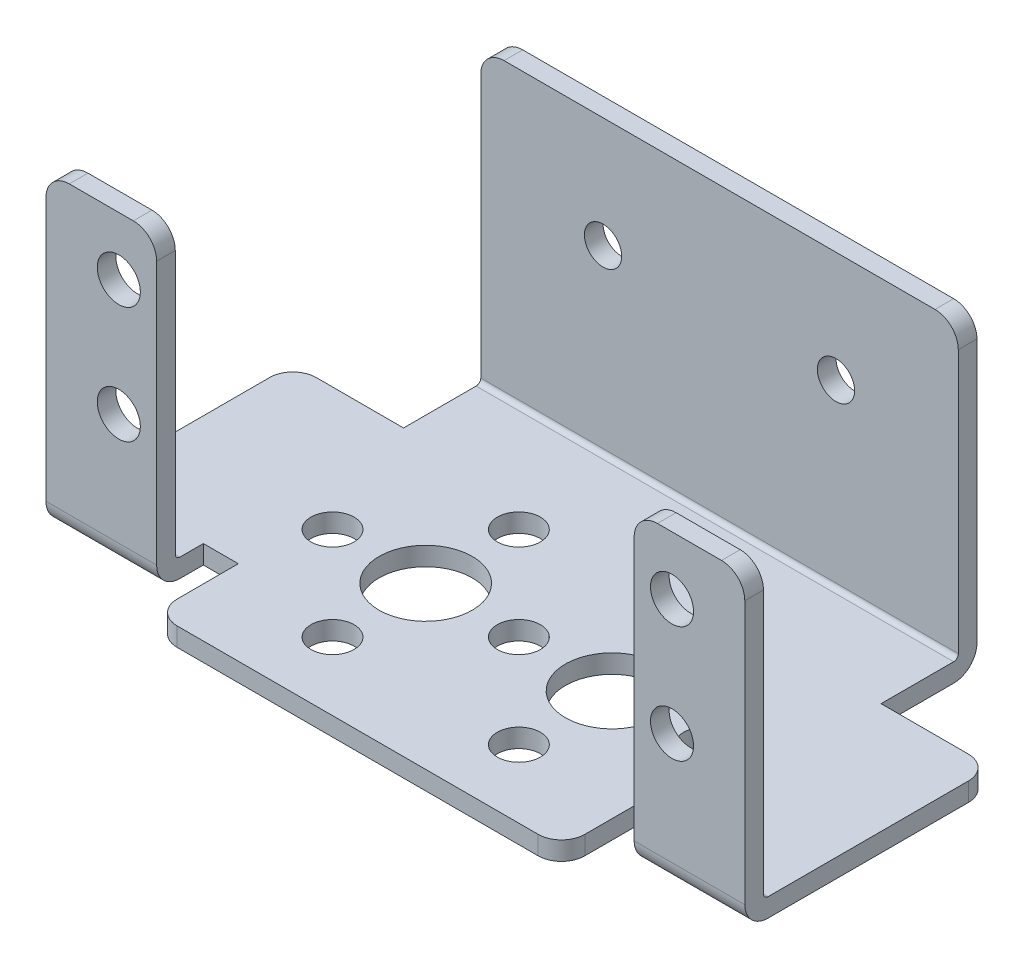
SolidWorks part; units mm, degrees
material "5052 Alloy"
ref_plane "Front Plane" through (0, 0, 0) normal (0, 0, 1) x (1, 0, 0)
ref_plane "Top Plane" through (0, 0, 0) normal (0, 1, 0) x (1, 0, 0)
ref_plane "Right Plane" through (0, 0, 0) normal (1, 0, 0) x (0, 0, -1)
sketch "Sketch1" plane through (0, 0, 0) normal (0, 1, 0) x (1, 0, 0)
  line L0 (-30, -10.6) -> (-30, 10.6)
  line L1 (-30, 10.6) -> (-20.5, 10.6)
  line L2 (-20.5, 10.6) -> (-20.5, 18.8307)
  line L3 (-20.5, 18.8307) -> (20.5, 18.8307)
  line L4 (20.5, 18.8307) -> (20.5, 10.6)
  line L5 (20.5, 10.6) -> (30, 10.6)
  line L6 (30, 10.6) -> (30, -10.6)
  line L7 (30, -10.6) -> (20.5, -10.6)
  line L8 (20.5, -10.6) -> (20.5, -6.588)
  line L9 (20.5, -6.588) -> (17.5, -6.588)
  line L10 (17.5, -6.588) -> (17.5, -13.8389)
  line L11 (17.5, -13.8389) -> (-17.5, -13.8389)
  line L12 (-17.5, -13.8389) -> (-17.5, -6.588)
  line L13 (-17.5, -6.588) -> (-20.5, -6.588)
  line L14 (-20.5, -6.588) -> (-20.5, -10.6)
  line L15 (-20.5, -10.6) -> (-30, -10.6)
  line L16 (-30, 0) -> (30, 0) construction
  line L17 (0, 18.8307) -> (0, -13.8389) construction
  dimension "D1" = 21.2
  dimension "D2" = 9.5
  dimension "D3" = 41
  dimension "D4" = 6.588
  dimension "D5" = 13.8389
  dimension "D6" = 9.5
  dimension "D8" = 35
  dimension "D9" = 3
  dimension "D11" = 29.4307
extrude "Extrude1" add sketch "Sketch1" along normal blind 1.6
sketch "Sketch2" plane through (0, 1.6, 0) normal (0, 1, 0) x (1, 0, 0)
  line L0 (-20.5, -10.6) -> (-20.5, -6.588) construction
  line L1 (-30, -10.6) -> (-20.5, -10.6)
  line L2 (-30, -10.6) -> (-30, -9)
  line L3 (-30, -9) -> (-20.5, -9)
  line L4 (-20.5, -10.6) -> (-20.5, -9)
  line L5 (30, -10.6) -> (30, 10.6) construction
  line L6 (20.5, -10.6) -> (30, -10.6)
  line L7 (20.5, -10.6) -> (20.5, -9)
  line L8 (20.5, -9) -> (30, -9)
  line L9 (30, -10.6) -> (30, -9)
  line L10 (20.5, 10.6) -> (20.5, 18.8307) construction
  line L11 (-20.5, 18.8307) -> (20.5, 18.8307)
  line L12 (-20.5, 18.8307) -> (-20.5, 17.2307)
  line L13 (-20.5, 17.2307) -> (20.5, 17.2307)
  line L14 (20.5, 18.8307) -> (20.5, 17.2307)
  dimension "D1" = 1.6
  dimension "D2" = 1.6
  dimension "D3" = 1.6
extrude "Extrude2" add sketch "Sketch2" along normal blind 25
fillet "Fillet2" radius 0.4 3 edges at (25.25, 1.6, 9) (0, 1.6, -17.2307)
fillet "Fillet3" radius 2 13 edges at (-30, 0.8, -10.6) (-17.5, 0.8, 13.8389) (30, 0.8, -10.6) (20.5, 26.6, 9.8) (30, 26.6, 9.8) (20.5, 26.6, -18.0307) (-20.5, 26.6, -18.0307) (-30, 26.6, 9.8) (-20.5, 26.6, 9.8) (-25.25, 0, 10.6) (25.25, 0, 10.6) (0, 0, -18.8307) (17.5, 0.8, 13.8389)
sketch "Sketch3" plane through (0, 0, 10.6) normal (0, 0, 1) x (1, 0, 0)
  line L0 (-30, 0) -> (-20.5, 0) construction
  line L3 (-23.75, 11.6) -> (23.75, 11.6) construction
  line L4 (23.75, 21.6) -> (-23.75, 21.6) construction
  line L5 (0, 11.6) -> (0, 21.6) construction
  circle A0 centre (-23.75, 21.6) radius 1.85
  circle A1 centre (-23.75, 11.6) radius 1.85
  circle A2 centre (23.75, 21.6) radius 1.85
  circle A3 centre (23.75, 11.6) radius 1.85
  dimension "D1" = 23.75
  dimension "D2" = 3.7
  dimension "D5" = 11.6
  dimension "D8" = 10
hole_wizard "Ø3.7 (3.7) Diameter Hole1" positions "Sketch7" profile "Sketch6" hole size "Ø3.7" standard "Ansi Metric" end condition through all
sketch "Sketch7" plane through (0, 0, 10.6) normal (0, 0, 1) x (1, 0, 0)
  point P0 (-23.75, 21.6)
  point P1 (-23.75, 11.6)
  point P4 (23.75, 11.6)
  point P7 (23.75, 21.6)
sketch "Sketch6" plane through (-23.75, 21.6, 10.6) normal (1, 0, 0) x (0, -1, 0)
  line L0 (0, 0) -> (0, 29.4307)
  line L1 (0, 29.4307) -> (1.85, 29.4307)
  line L2 (1.85, 29.4307) -> (1.85, 0)
  line L5 (1.85, 0) -> (0, 0)
  line L11 (0, -6.35) -> (0, 107.95) construction
  dimension "Thru Hole Dia." = 3.7
  dimension "Thru Hole Depth" = 29.4307
sketch "Sketch4" plane through (0, 0, -17.2307) normal (0, 0, 1) x (1, 0, 0)
  line L0 (0, 0) -> (0, 17.0945) construction
  line L1 (-10, 17.0945) -> (10, 17.0945) construction
  line L2 (-15.5, 0) -> (15.5, 0) construction
  circle A0 centre (10, 17.0945) radius 1.6
  circle A1 centre (-10, 17.0945) radius 1.6
  dimension "D2" = 3.2
  dimension "D1" = 10
  dimension "D3" = 17.0945
extrude "Cut-Extrude2" cut sketch "Sketch4" against normal through all
sketch "Sketch5" plane through (0, 1.6, 0) normal (0, 1, 0) x (1, 0, 0)
  line L2 (-8, 0) -> (8, 0) construction
  point P3 (0, 0)
  line B0 (8, 0) -> (8, 8) construction
  circle B1 centre (8, 0) radius 4
  circle B2 centre (8, 8) radius 1.85
  circle B3 centre (8, 0) radius 8 construction
  line B4 (-8, 0) -> (-8, 8) construction
  circle B5 centre (-8, 0) radius 4
  circle B6 centre (-8, 8) radius 1.85
  circle B7 centre (-8, 0) radius 8 construction
  dimension "D1" = 16
sketch_block_instance "Block-Tetrix Hole Pattern - 8x8x3.7-1"
sketch_block "Block-Tetrix Hole Pattern - 8x8x3.7" parameters "D1"=3.7, "D2"=8, "D3"=16
sketch_block_instance "Block-Tetrix Hole Pattern - 8x8x3.7-3"
extrude "Cut-Extrude3" cut sketch "Sketch5" against normal through all contours B1 | B5 region at (8, 1.6, 0) region at (-8, 1.6, 0)
extrude "Cut-Extrude4" cut sketch "Sketch5<3>" against normal through all contours B2 region at (8, 1.6, -8)
sketch "Sketch5<3>" plane through (0, 1.6, 0) normal (0, 1, 0) x (1, 0, 0) same geometry as "Sketch5"
pattern_circular "CirPattern1" count 4 over 360 about axis through (8, 0, 0) along (0, 1, 0) of "Cut-Extrude4"
extrude "Cut-Extrude5" cut sketch "Sketch5<4>" against normal blind 10 contours B6 region at (-8, 1.6, -8)
sketch "Sketch5<4>" plane through (0, 1.6, 0) normal (0, 1, 0) x (1, 0, 0) same geometry as "Sketch5"
pattern_circular "CirPattern2" count 4 over 360 about axis through (-8, 0, 0) along (0, 1, 0) of "Cut-Extrude5"
